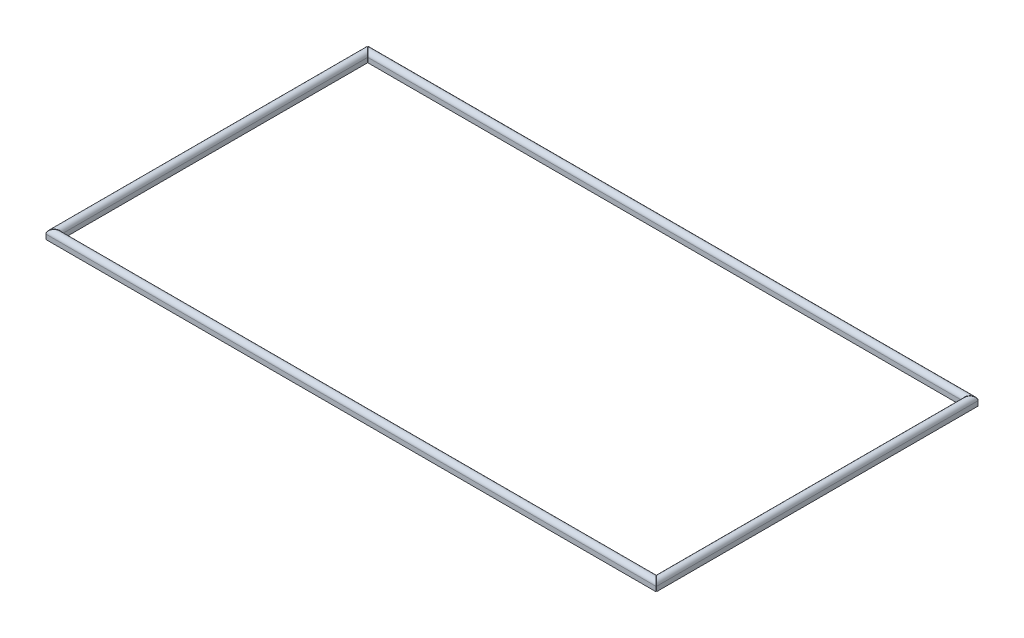
SolidWorks part; units mm, degrees
ref_plane "Front Plane" through (0, 0, 0) normal (0, 0, 1) x (1, 0, 0)
ref_plane "Top Plane" through (0, 0, 0) normal (0, 1, 0) x (1, 0, 0)
ref_plane "Right Plane" through (0, 0, 0) normal (1, 0, 0) x (0, 0, -1)
sketch "Croquis1" plane through (0, 0, 0) normal (0, 1, 0) x (1, 0, 0)
  line L0 (0, 0) -> (0, 12)
  line L1 (0, 12) -> (910, 12)
  line L2 (910, 12) -> (910, 0)
  line L3 (910, 0) -> (0, 0)
  line L4 (910, 12) -> (910, 480)
  line L5 (910, 480) -> (0, 480)
  line L6 (0, 480) -> (0, 12)
  line L7 (898, 12) -> (898, 468)
  line L8 (898, 468) -> (12, 468)
  line L9 (12, 468) -> (12, 12)
  dimension "D1" = 12
  dimension "D2" = 910
  dimension "D3" = 12
  dimension "D4" = 12
  dimension "D5" = 12
  dimension "D6" = 480
extrude "Saliente-Extruir1" add sketch "Croquis1" along normal blind 13 contours L9 L8 L7 L1 L4 L5 L6 | L3 L2 L1 L0 region at (455, 0, -6) region at (10.2329, 0, -246)
sketch "Croquis2" plane through (0, 13, 0) normal (0, 1, 0) x (1, 0, 0)
  line L0 (12, 468) -> (0, 480)
  line L1 (0, 480) -> (0, 479.5)
  line L2 (0, 480) -> (0, 0) construction
  line L3 (0, 479.5) -> (12, 467.5)
  line L4 (12, 468) -> (12, 12) construction
  line L5 (12, 467.5) -> (12, 468)
  line L6 (12.5, 468) -> (0.5, 480)
  line L7 (898, 468) -> (12, 468) construction
  line L8 (910, 480) -> (0, 480) construction
  line L9 (0.5, 480) -> (0, 480)
  line L10 (12.5, 468) -> (12, 468)
  line L11 (12, 240) -> (512.6656, 240) construction
  line L12 (455, 468) -> (455, 240) construction
  line L13 (12.5, 12) -> (12, 12)
  line L14 (0.5, 0) -> (0, 0)
  line L15 (12.5, 12) -> (0.5, 0)
  line L16 (12, 12.5) -> (12, 12)
  line L17 (0, 0.5) -> (12, 12.5)
  line L18 (0, 0) -> (0, 0.5)
  line L19 (12, 12) -> (0, 0)
  line L34 (897.5, 468) -> (898, 468)
  line L35 (909.5, 480) -> (910, 480)
  line L36 (897.5, 468) -> (909.5, 480)
  line L37 (898, 467.5) -> (898, 468)
  line L38 (910, 479.5) -> (898, 467.5)
  line L39 (910, 480) -> (910, 479.5)
  line L40 (898, 468) -> (910, 480)
  line L48 (898, 12) -> (910, 0)
  line L49 (910, 0) -> (910, 0.5)
  line L50 (910, 0.5) -> (898, 12.5)
  line L51 (898, 12.5) -> (898, 12)
  line L52 (897.5, 12) -> (909.5, 0)
  line L53 (909.5, 0) -> (910, 0)
  line L54 (897.5, 12) -> (898, 12)
  line M6 (0, 0) -> (910, 0)
  line M7 (910, 0) -> (910, 480)
  line M8 (910, 480) -> (0, 480)
  line M9 (0, 480) -> (0, 0)
  line M10 (12, 12) -> (12, 468)
  line M11 (12, 468) -> (898, 468)
  line M12 (898, 468) -> (898, 12)
  line M13 (898, 12) -> (12, 12)
  dimension "D1" = 0.5
  dimension "D2" = 0.5
  dimension "D3" = 0.5
extrude "Cortar-Extruir1" cut sketch "Croquis2" against normal blind 40 contours L3 L0 M9 M10 | L6 L0 M11 M8 | L19 L17 M10 M9 | L19 L15 M13 M6 | L40 L38 M12 M7 | L40 L36 M11 M8 | L50 L48 M7 M12 | L52 L48 M13 M6 region at (6, 13, -473.75) region at (6.25, 13, -474) region at (6, 13, -6.25) region at (903.75, 13, -474) region at (6.25, 13, -6) region at (904, 13, -473.75) region at (903.75, 13, -6) region at (904, 13, -6.25)
fillet "Redondeo6" 2 edges at (455, 13, -480) (455, 13, -468) type full round first side face at (455, 6.5, -480) second side face at (455, 6.5, -468) middle face at (455, 13, -474)
fillet "Redondeo7" 2 edges at (12, 13, -240) (0, 13, -240) type full round first side face at (12, 6.5, -240) second side face at (0, 6.5, -240) middle face at (6, 13, -240)
fillet "Redondeo8" 2 edges at (455, 13, -12) (455, 13, 0) type full round first side face at (455, 6.5, -12) second side face at (455, 6.5, 0) middle face at (455, 13, -6)
fillet "Redondeo9" 2 edges at (898, 13, -240) (910, 13, -240) type full round first side face at (898, 6.5, -240) second side face at (910, 6.5, -240) middle face at (904, 13, -240)
